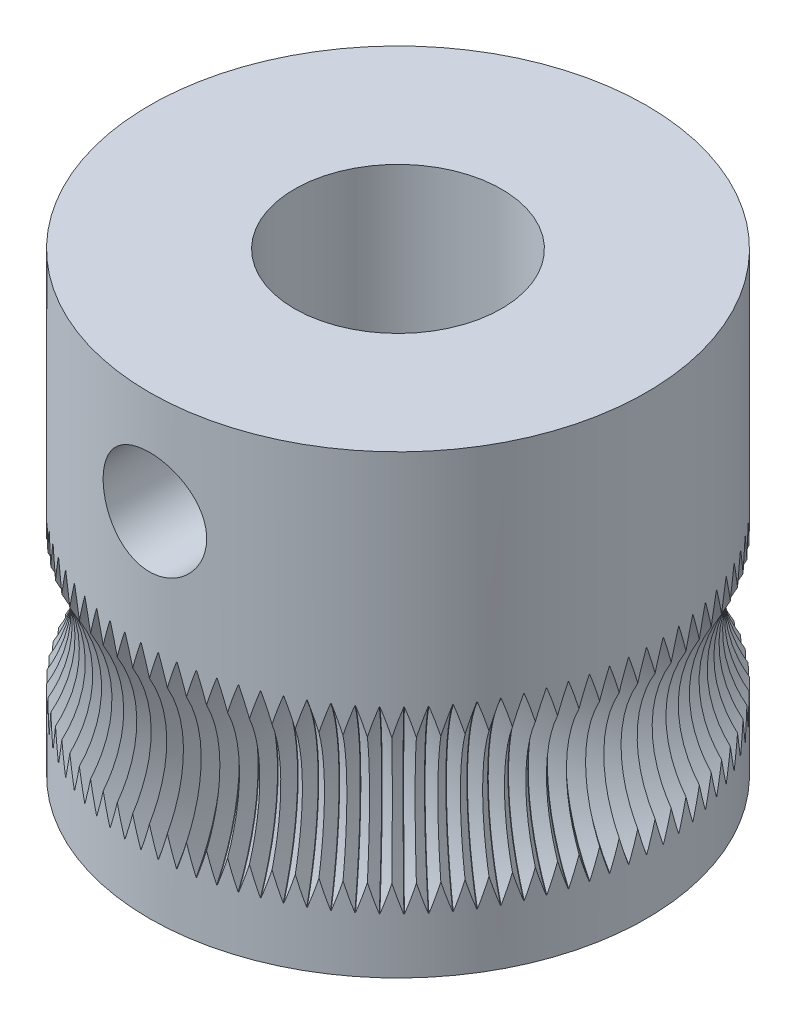
SolidWorks part; units mm, degrees
ref_plane "Front Plane" through (0, 0, 0) normal (0, 0, 1) x (1, 0, 0)
ref_plane "Top Plane" through (0, 0, 0) normal (0, 1, 0) x (1, 0, 0)
ref_plane "Right Plane" through (0, 0, 0) normal (1, 0, 0) x (0, 0, -1)
sketch "Sketch1" plane through (0, 0, 0) normal (0, 1, 0) x (1, 0, 0)
  circle A0 centre (0, 0) radius 6
  circle A1 centre (0, 0) radius 2.5
  dimension "D1" = 12
  dimension "D2" = 5
extrude "Boss-Extrude1" add sketch "Sketch1" along normal blind 11
ref_plane "Plane1" through (0, 0, 6) normal (0, 0, 1) x (1, 0, 0)
ref_axis "Axis1" through (0, 11, 0) along (0, -1, 0)
hole_wizard "M3 Tapped Hole1" positions "Sketch6" profile "Sketch7" tap size "M3" standard "ISO" end condition up to next
sketch "Sketch6" plane through (0, 0, 6) normal (0, 0, 1) x (1, 0, 0)
  line L0 (6, 11) -> (-6, 11) construction
  line L1 (0, 11) -> (0, 0) construction
  point P1 (0, 8.5)
  dimension "D1" = 2.5
cosmetic thread "Hole Thread1" parameters "D2"=3
sketch "Sketch7" plane through (0, 8.5, 6) normal (1, 0, 0) x (0, -1, 0)
  line L0 (0, 0) -> (0, 3.5)
  line L1 (0, 3.5) -> (1.25, 3.5)
  line L2 (1.25, 3.5) -> (1.25, 0)
  line L5 (1.25, 0) -> (0, 0)
  line L11 (0, -6.35) -> (0, 107.95) construction
  dimension "Thru Tap Drill Dia." = 2.5
  dimension "Thru Tap Drill Depth" = 3.5
ref_plane "Plane3" through (0, 0, 0) normal (0, 0, 1) x (1, 0, 0)
sketch "Sketch8" plane through (0, 0, 0) normal (0, 0, 1) x (1, 0, 0)
  line L0 (0, 11) -> (0, 0) construction
  line L1 (6, 11) -> (-6, 11) construction
  line L2 (8.75, 3.5) -> (8.75, 8.3641) construction
  circle A0 centre (8.75, 3.5) radius 3.5
  point P6 (8.75, 7)
  dimension "D1" = 7
  dimension "D2" = 8.75
  dimension "D3" = 7.5
ref_plane "Plane4" through (8.75, 0, 0) normal (1, 0, 0) x (0, 0, -1)
sketch "Sketch10" plane through (8.75, 0, 0) normal (1, 0, 0) x (0, 0, -1)
  line L0 (-0.9697, 5.3292) -> (0.9697, 5.3292)
  line L1 (0.9697, 5.3292) -> (0.005, 7)
  line L2 (0.005, 7) -> (-0.005, 7)
  line L3 (-0.005, 7) -> (-0.9697, 5.3292)
  line L6 (0, 3.5) -> (0, 8.3641) construction
  point P2 (0, 7)
  point P5 (0, 5.3292)
  dimension "D1" = 0.01
  dimension "D2" = 60
sweep "Cut-Sweep1" cut profiles "Sketch10" path "Sketch8"
pattern_circular "CirPattern1" count 90 over 360 about axis through (0, 11, 0) along (0, -1, 0) of "Cut-Sweep1"
